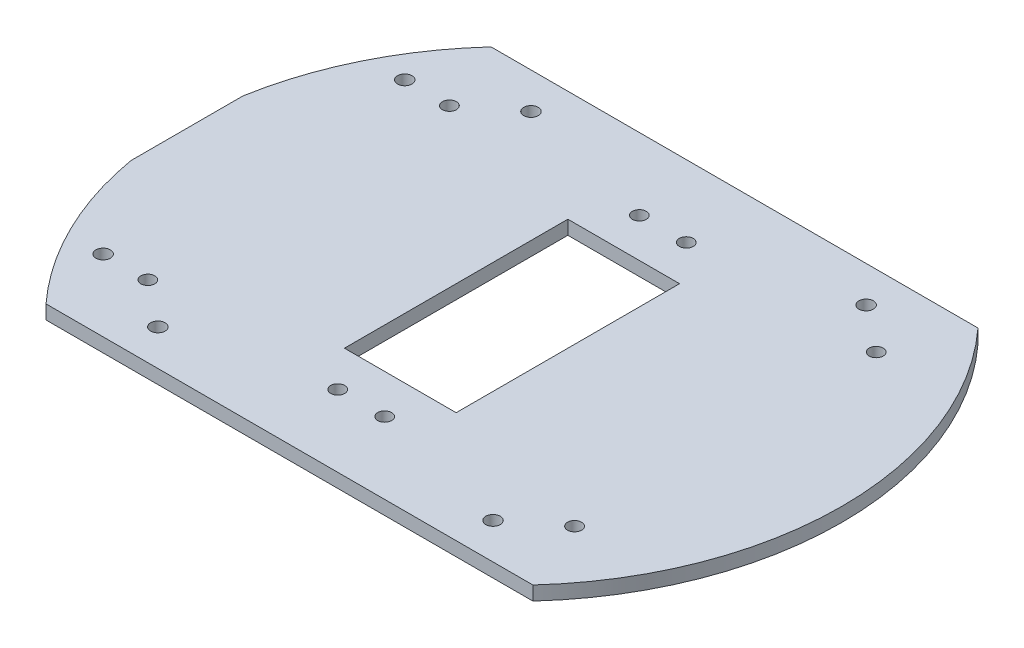
SolidWorks part; units mm, degrees
material "Acrylic (Medium-high impact)"
ref_plane "Front Plane" through (0, 0, 0) normal (0, 0, 1) x (1, 0, 0)
ref_plane "Top Plane" through (0, 0, 0) normal (0, 1, 0) x (1, 0, 0)
ref_plane "Right Plane" through (0, 0, 0) normal (1, 0, 0) x (0, 0, -1)
sketch "Sketch1" plane through (0, 0, 0) normal (0, 1, 0) x (1, 0, 0)
  line L0 (-73.9169, 12.7) -> (-73.9169, -12.7)
  line L2 (-55.356, -50.6035) -> (55.356, -50.6035)
  line L3 (-55.356, 50.6035) -> (55.356, 50.6035)
  line L4 (-48.5169, -34.29) -> (-48.5169, 34.29) construction
  line L5 (-48.5169, 34.29) -> (-5.3369, 34.29) construction
  line L6 (-5.3369, 34.29) -> (-5.3369, -34.29) construction
  line L7 (-5.3369, -34.29) -> (-48.5169, -34.29) construction
  line L8 (-73.9169, 0) -> (-48.5169, 0) construction
  line L9 (0, 50.6035) -> (0, -51.6195) construction
  line L11 (-12.7, 25.4) -> (12.7, 25.4)
  line L12 (-12.7, 25.4) -> (-12.7, -25.4)
  line L13 (-12.7, -25.4) -> (12.7, -25.4)
  line L14 (12.7, 25.4) -> (12.7, -25.4)
  line L15 (0, 0) -> (0, 25.4) construction
  line L16 (0, 0) -> (-12.7, 0) construction
  arc A0 (-73.9169, -12.7) -> (-55.356, -50.6035) centre (0, 0) ccw
  arc A2 (-55.356, 50.6035) -> (-73.9169, 12.7) centre (0, 0) ccw
  arc A3 (55.356, -50.6035) -> (55.356, 50.6035) centre (0, 0) ccw
  circle A4 centre (-58.6769, -34.29) radius 1.651
  circle A5 centre (-58.6769, 34.29) radius 1.651
  circle A6 centre (-38.1, 42.418) radius 1.651
  circle A7 centre (38.1, 42.418) radius 1.651
  circle A8 centre (-38.1, -42.418) radius 1.651
  circle A9 centre (38.1, -42.418) radius 1.651
  circle A11 centre (-58.6769, 34.29) radius 1.651 construction
  circle A12 centre (-48.5169, 34.29) radius 1.5875
  circle A13 centre (-5.3369, 34.29) radius 1.5875
  circle A14 centre (-5.3369, -34.29) radius 1.5875
  circle A15 centre (-48.5169, -34.29) radius 1.5875
  circle A16 centre (5.3369, -34.29) radius 1.5875
  circle A17 centre (48.5169, -34.29) radius 1.5875
  circle A18 centre (48.5169, 34.29) radius 1.5875
  circle A19 centre (5.3369, 34.29) radius 1.5875
  dimension "D3" = 3.175
  dimension "D1" = 43.18
  dimension "D2" = 68.58
  dimension "D4" = 25.4
  dimension "D5" = 25.4
  dimension "D6" = 50.8
extrude "Boss-Extrude1" add sketch "Sketch1" along normal blind 3.175
